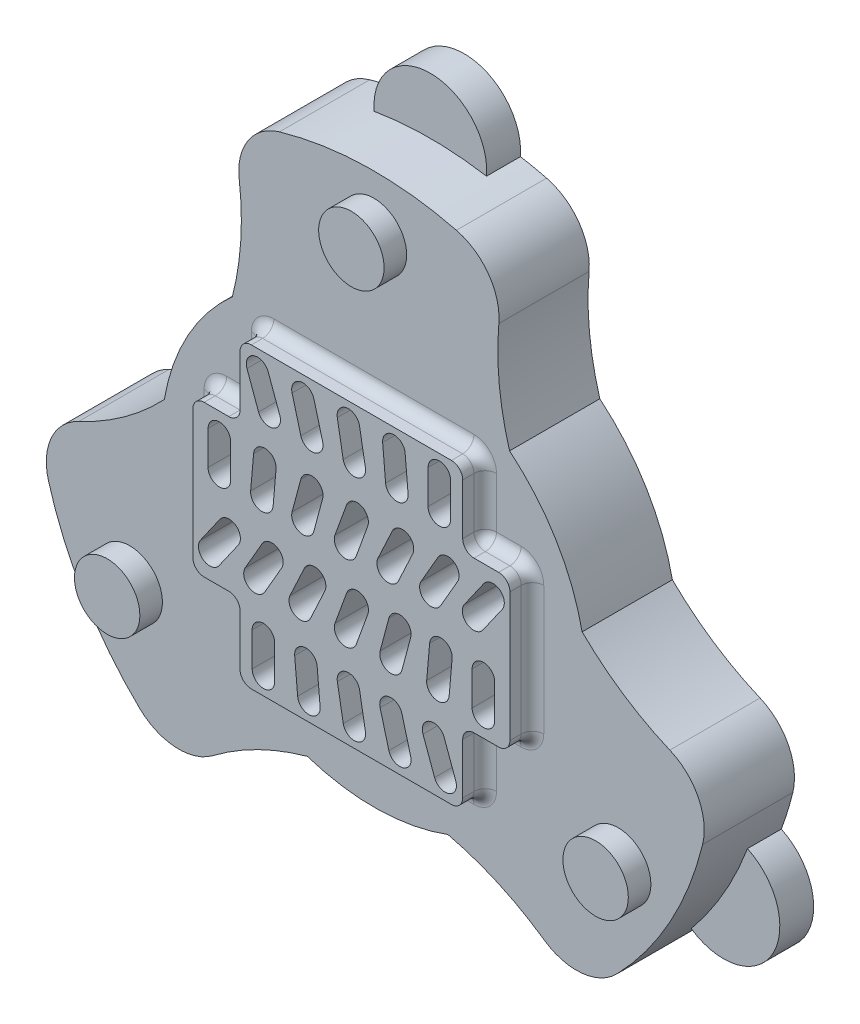
SolidWorks part; units mm, degrees
ref_plane "Спереди" through (0, 0, 0) normal (0, 0, 1) x (1, 0, 0)
ref_plane "Сверху" through (0, 0, 0) normal (0, 1, 0) x (1, 0, 0)
ref_plane "Справа" through (0, 0, 0) normal (1, 0, 0) x (0, 0, -1)
sketch "Sketch1" plane through (0, 0, 0) normal (0, 0, 1) x (1, 0, 0)
  line L0 (3.9, 6.755) -> (7.8, 0) construction
  line L2 (5.85, 10.1325) -> (11.7, 0) construction
  line L4 (7.8, 13.51) -> (15.6, 0) construction
  circle A61 centre (0, 0) radius 20
  circle A131 centre (0, 0) radius 1.25
  circle A484 centre (3.9, 0) radius 1.25
  circle A485 centre (7.8, 0) radius 1.25
  circle A486 centre (11.7, 0) radius 1.25
  circle A487 centre (15.6, 0) radius 1.25
  circle A488 centre (1.95, -3.3775) radius 1.25
  circle A489 centre (3.9, -6.755) radius 1.25
  circle A490 centre (5.85, -10.1325) radius 1.25
  circle A491 centre (7.8, -13.51) radius 1.25
  circle A492 centre (-1.95, -3.3775) radius 1.25
  circle A493 centre (-3.9, -6.755) radius 1.25
  circle A494 centre (-5.85, -10.1325) radius 1.25
  circle A495 centre (-7.8, -13.51) radius 1.25
  circle A496 centre (-3.9, 0) radius 1.25
  circle A497 centre (-7.8, 0) radius 1.25
  circle A498 centre (-11.7, 0) radius 1.25
  circle A499 centre (-15.6, 0) radius 1.25
  circle A500 centre (-1.95, 3.3775) radius 1.25
  circle A501 centre (-3.9, 6.755) radius 1.25
  circle A502 centre (-5.85, 10.1325) radius 1.25
  circle A503 centre (-7.8, 13.51) radius 1.25
  circle A504 centre (1.95, 3.3775) radius 1.25
  circle A505 centre (3.9, 6.755) radius 1.25
  circle A506 centre (5.85, 10.1325) radius 1.25
  circle A507 centre (7.8, 13.51) radius 1.25
  circle A508 centre (5.85, 3.3775) radius 1.25
  circle A509 centre (7.8, 6.755) radius 1.25
  circle A510 centre (9.75, 3.3775) radius 1.25
  circle A511 centre (11.7, 6.755) radius 1.25
  circle A512 centre (9.7491, 10.1341) radius 1.25
  circle A513 centre (13.6509, 3.3759) radius 1.25
  circle A514 centre (5.85, -3.3791) radius 1.25
  circle A515 centre (9.75, -3.3791) radius 1.25
  circle A516 centre (7.8, -6.7566) radius 1.25
  circle A517 centre (11.7, -6.7566) radius 1.25
  circle A518 centre (9.7491, -10.1356) radius 1.25
  circle A519 centre (13.6509, -3.3775) radius 1.25
  circle A520 centre (-0.0013, -6.7573) radius 1.25
  circle A521 centre (1.9487, -10.1348) radius 1.25
  circle A522 centre (-1.9513, -10.1348) radius 1.25
  circle A523 centre (-0.0013, -13.5123) radius 1.25
  circle A524 centre (-3.9032, -13.5123) radius 1.25
  circle A525 centre (3.9005, -13.5123) radius 1.25
  circle A526 centre (-5.8527, -3.3791) radius 1.25
  circle A527 centre (-7.8027, -6.7566) radius 1.25
  circle A528 centre (-9.7527, -3.3791) radius 1.25
  circle A529 centre (-11.7027, -6.7566) radius 1.25
  circle A530 centre (-13.6536, -3.3775) radius 1.25
  circle A531 centre (-9.7518, -10.1356) radius 1.25
  circle A532 centre (-5.8527, 3.3775) radius 1.25
  circle A533 centre (-9.7527, 3.3775) radius 1.25
  circle A534 centre (-7.8027, 6.755) radius 1.25
  circle A535 centre (-11.7027, 6.755) radius 1.25
  circle A536 centre (-9.7518, 10.1341) radius 1.25
  circle A537 centre (-13.6536, 3.3759) radius 1.25
  circle A538 centre (-0.0014, 6.7558) radius 1.25
  circle A539 centre (-1.9514, 10.1333) radius 1.25
  circle A540 centre (1.9486, 10.1333) radius 1.25
  circle A541 centre (-0.0014, 13.5108) radius 1.25
  circle A542 centre (3.9005, 13.5108) radius 1.25
  circle A543 centre (-3.9032, 13.5108) radius 1.25
  circle A544 centre (13.65, -1.1258) radius 2.2517 construction
  circle A545 centre (11.7009, -4.5044) radius 2.2522 construction
  circle A546 centre (9.75, -7.8834) radius 2.2522 construction
  circle A547 centre (7.7987, -11.2591) radius 2.2509 construction
  circle A548 centre (13.65, -1.1258) radius 0.65
  circle A549 centre (11.7009, -4.5044) radius 0.65
  circle A550 centre (9.75, -7.8834) radius 0.65
  circle A551 centre (7.7987, -11.2591) radius 0.65
  circle A552 centre (9.75, -1.1258) radius 0.65
  circle A553 centre (7.8009, -4.5044) radius 0.65
  circle A554 centre (5.85, -7.8834) radius 0.65
  circle A555 centre (3.8987, -11.2591) radius 0.65
  circle A556 centre (5.85, -1.1258) radius 0.65
  circle A557 centre (3.9009, -4.5044) radius 0.65
  circle A558 centre (1.95, -7.8834) radius 0.65
  circle A559 centre (-0.0013, -11.2591) radius 0.65
  circle A560 centre (1.95, -1.1258) radius 0.65
  circle A561 centre (0.0009, -4.5044) radius 0.65
  circle A562 centre (-1.95, -7.8834) radius 0.65
  circle A563 centre (-3.9013, -11.2591) radius 0.65
  circle A564 centre (-1.95, -1.1258) radius 0.65
  circle A565 centre (-3.8991, -4.5044) radius 0.65
  circle A566 centre (-5.85, -7.8834) radius 0.65
  circle A567 centre (-7.8013, -11.2591) radius 0.65
  circle A568 centre (-5.85, -1.1258) radius 0.65
  circle A569 centre (-7.7991, -4.5044) radius 0.65
  circle A570 centre (-9.75, -7.8834) radius 0.65
  circle A572 centre (-9.75, -1.1258) radius 0.65
  circle A573 centre (-11.6991, -4.5044) radius 0.65
  circle A576 centre (-13.65, -1.1258) radius 0.65
  circle A587 centre (0, 2.2517) radius 2.2517 construction
  circle A588 centre (0, 2.2517) radius 0.65
  circle A589 centre (3.9, 2.2517) radius 0.65
  circle A590 centre (7.8, 2.2517) radius 0.65
  circle A591 centre (11.7, 2.2517) radius 0.65
  circle A592 centre (15.6, 2.2517) radius 0.65
  circle A593 centre (1.9491, 5.6297) radius 2.2522 construction
  circle A594 centre (1.9491, 5.6297) radius 0.65
  circle A595 centre (5.8491, 5.6297) radius 0.65
  circle A596 centre (9.7491, 5.6297) radius 0.65
  circle A597 centre (13.6491, 5.6297) radius 0.65
  circle A598 centre (3.8991, 9.0072) radius 2.2522 construction
  circle A599 centre (3.8991, 9.0072) radius 0.65
  circle A600 centre (7.7991, 9.0072) radius 0.65
  circle A601 centre (11.6991, 9.0072) radius 0.65
  circle A602 centre (5.85, 12.3842) radius 2.2517 construction
  circle A603 centre (5.85, 12.3842) radius 0.65
  circle A604 centre (9.75, 12.3842) radius 0.65
  circle A605 centre (5.85, -14.6358) radius 0.65
  circle A606 centre (1.9509, -14.6353) radius 0.65
  circle A607 centre (-1.9491, -14.6353) radius 0.65
  circle A608 centre (-5.85, -14.6358) radius 0.65
  circle A609 centre (-15.6, 2.2517) radius 0.65
  circle A610 centre (-13.65, 5.6281) radius 0.65
  circle A611 centre (-11.7, 9.0056) radius 0.65
  circle A612 centre (-9.75, 12.3842) radius 0.65
  circle A613 centre (-5.85, 12.3842) radius 0.65
  circle A614 centre (-1.95, 12.3842) radius 0.65
  circle A615 centre (1.95, 12.3842) radius 0.65
  circle A616 centre (-7.8, 9.0056) radius 0.65
  circle A617 centre (-9.75, 5.6281) radius 0.65
  circle A618 centre (-11.7, 2.2517) radius 0.65
  circle A619 centre (-3.9, 9.0056) radius 0.65
  circle A620 centre (-5.85, 5.6281) radius 0.65
  circle A621 centre (-7.8, 2.2517) radius 0.65
  circle A622 centre (0, 9.0056) radius 0.65
  circle A623 centre (-1.95, 5.6281) radius 0.65
  circle A624 centre (-3.9, 2.2517) radius 0.65
  circle A625 centre (-15.5991, -4.5044) radius 0.65
  circle A626 centre (-13.65, -7.8834) radius 0.65
  circle A627 centre (-17.55, -7.8834) radius 0.65
  circle A628 centre (-19.5013, -11.2591) radius 0.65
  circle A629 centre (-15.6013, -11.2591) radius 0.65
  circle A630 centre (-11.7013, -11.2591) radius 0.65
  point P51 (0, 0)
  point P125 (-0.0013, -0.0008)
  point P231 (0, 0)
  dimension "D1" = 5
  dimension "D3" = 6
  dimension "D5" = 8
  dimension "D7" = 4
  dimension "D11" = 4
  dimension "D2" = 6
  dimension "D6" = 5
  dimension "D8" = 3
  dimension "D9" = 2
  dimension "D4" = 1.3
  dimension "D10" = 3
ref_plane "Plane1" through (0, 0, 10) normal (0, 0, 1) x (1, 0, 0)
sketch "Sketch2" plane through (0, 0, 10) normal (0, 0, 1) x (1, 0, 0)
  line L2 (8.0291, 21.9345) -> (-10.7971, 21.9345) construction
  circle A52 centre (0, 0) radius 16.85 construction
  circle A53 centre (0, 0) radius 18.85
  point P5 (0, 0)
  line B0 (4.7641, 11.7139) -> (5.0256, 8.7254)
  arc B1 (3.0332, 8.551) -> (5.0256, 8.7254) centre (4.0294, 8.6382) ccw
  line B2 (2.7717, 11.5396) -> (3.0332, 8.551)
  arc B3 (4.7641, 11.7139) -> (2.7717, 11.5396) centre (3.7679, 11.6268) ccw
  line B4 (3.7679, 11.6268) -> (4.0294, 8.6382) construction
  line B5 (0.722, 11.7838) -> (1.2429, 8.8293)
  arc B6 (-0.7267, 8.482) -> (1.2429, 8.8293) centre (0.2581, 8.6557) ccw
  line B7 (-1.2476, 11.4365) -> (-0.7267, 8.482)
  arc B8 (0.722, 11.7838) -> (-1.2476, 11.4365) centre (-0.2628, 11.6101) ccw
  line B9 (-0.2628, 11.6101) -> (0.2581, 8.6557) construction
  line B10 (-3.3247, 11.8406) -> (-2.5482, 8.9428)
  arc B11 (-4.48, 8.4252) -> (-2.5482, 8.9428) centre (-3.5141, 8.684) ccw
  line B12 (-5.2565, 11.323) -> (-4.48, 8.4252)
  arc B13 (-3.3247, 11.8406) -> (-5.2565, 11.323) centre (-4.2906, 11.5818) ccw
  line B14 (-4.2906, 11.5818) -> (-3.5141, 8.684) construction
  line B15 (-7.3747, 11.8841) -> (-6.3486, 9.065)
  arc B16 (-8.228, 8.3809) -> (-6.3486, 9.065) centre (-7.2883, 8.723) ccw
  line B17 (-9.2541, 11.2) -> (-8.228, 8.3809)
  arc B18 (-7.3747, 11.8841) -> (-9.2541, 11.2) centre (-8.3144, 11.542) ccw
  line B19 (-8.3144, 11.542) -> (-7.2883, 8.723) construction
  line B20 (10.0165, 2.7228) -> (11.7373, 5.1803)
  arc B21 (13.3756, 4.0332) -> (11.7373, 5.1803) centre (12.5564, 4.6067) ccw
  line B22 (11.6548, 1.5757) -> (13.3756, 4.0332)
  arc B23 (10.0165, 2.7228) -> (11.6548, 1.5757) centre (10.8357, 2.1493) ccw
  line B24 (10.8357, 2.1493) -> (12.5564, 4.6067) construction
  line B25 (6.18, 2.579) -> (7.68, 5.177)
  arc B26 (9.4121, 4.177) -> (7.68, 5.177) centre (8.546, 4.677) ccw
  line B27 (7.9121, 1.579) -> (9.4121, 4.177)
  arc B28 (6.18, 2.579) -> (7.9121, 1.579) centre (7.046, 2.079) ccw
  line B29 (7.046, 2.079) -> (8.546, 4.677) construction
  line B30 (2.3558, 2.4412) -> (3.6237, 5.1601)
  arc B31 (5.4363, 4.3148) -> (3.6237, 5.1601) centre (4.53, 4.7375) ccw
  line B32 (4.1684, 1.5959) -> (5.4363, 4.3148)
  arc B33 (2.3558, 2.4412) -> (4.1684, 1.5959) centre (3.2621, 2.0185) ccw
  line B34 (3.2621, 2.0185) -> (4.53, 4.7375) construction
  line B35 (-1.4567, 2.3105) -> (-0.4306, 5.1296)
  arc B36 (1.4488, 4.4455) -> (-0.4306, 5.1296) centre (0.5091, 4.7875) ccw
  line B37 (0.4227, 1.6264) -> (1.4488, 4.4455)
  arc B38 (-1.4567, 2.3105) -> (0.4227, 1.6264) centre (-0.517, 1.9685) ccw
  line B39 (-0.517, 1.9685) -> (0.5091, 4.7875) construction
  line B40 (-5.2581, 2.1879) -> (-4.4816, 5.0857)
  arc B41 (-2.5498, 4.5681) -> (-4.4816, 5.0857) centre (-3.5157, 4.8269) ccw
  line B42 (-3.3263, 1.6703) -> (-2.5498, 4.5681)
  arc B43 (-5.2581, 2.1879) -> (-3.3263, 1.6703) centre (-4.2922, 1.9291) ccw
  line B44 (-4.2922, 1.9291) -> (-3.5157, 4.8269) construction
  line B45 (-8.9296, 1.9704) -> (-8.6682, 4.9589)
  arc B46 (-6.6758, 4.7846) -> (-8.6682, 4.9589) centre (-7.672, 4.8718) ccw
  line B47 (-6.9372, 1.7961) -> (-6.6758, 4.7846)
  arc B48 (-8.9296, 1.9704) -> (-6.9372, 1.7961) centre (-7.9334, 1.8832) ccw
  line B49 (-7.9334, 1.8832) -> (-7.672, 4.8718) construction
  line B50 (-12.704, 1.878) -> (-12.704, 4.878)
  arc B51 (-10.704, 4.878) -> (-12.704, 4.878) centre (-11.704, 4.878) ccw
  line B52 (-10.704, 1.878) -> (-10.704, 4.878)
  arc B53 (-12.704, 1.878) -> (-10.704, 1.878) centre (-11.704, 1.878) ccw
  line B54 (-11.704, 1.878) -> (-11.704, 4.878) construction
  line B55 (8.7976, 11.6329) -> (8.7976, 8.6329)
  arc B56 (6.7976, 8.6329) -> (8.7976, 8.6329) centre (7.7976, 8.6329) ccw
  line B57 (6.7976, 11.6329) -> (6.7976, 8.6329)
  arc B58 (8.7976, 11.6329) -> (6.7976, 11.6329) centre (7.7976, 11.6329) ccw
  line B59 (-4.7641, -11.7139) -> (-5.0256, -8.7254)
  arc B60 (-3.0332, -8.551) -> (-5.0256, -8.7254) centre (-4.0294, -8.6382) ccw
  line B61 (-2.7717, -11.5396) -> (-3.0332, -8.551)
  arc B62 (-4.7641, -11.7139) -> (-2.7717, -11.5396) centre (-3.7679, -11.6268) ccw
  line B63 (-0.722, -11.7838) -> (-1.2429, -8.8293)
  arc B64 (0.7267, -8.482) -> (-1.2429, -8.8293) centre (-0.2581, -8.6557) ccw
  line B65 (1.2476, -11.4365) -> (0.7267, -8.482)
  arc B66 (-0.722, -11.7838) -> (1.2476, -11.4365) centre (0.2628, -11.6101) ccw
  line B67 (3.3247, -11.8406) -> (2.5482, -8.9428)
  arc B68 (4.48, -8.4252) -> (2.5482, -8.9428) centre (3.5141, -8.684) ccw
  line B69 (5.2565, -11.323) -> (4.48, -8.4252)
  arc B70 (3.3247, -11.8406) -> (5.2565, -11.323) centre (4.2906, -11.5818) ccw
  line B71 (7.3747, -11.8841) -> (6.3486, -9.065)
  arc B72 (8.228, -8.3809) -> (6.3486, -9.065) centre (7.2883, -8.723) ccw
  line B73 (9.2541, -11.2) -> (8.228, -8.3809)
  arc B74 (7.3747, -11.8841) -> (9.2541, -11.2) centre (8.3144, -11.542) ccw
  line B75 (-10.0165, -2.7228) -> (-11.7373, -5.1803)
  arc B76 (-13.3756, -4.0332) -> (-11.7373, -5.1803) centre (-12.5564, -4.6067) ccw
  line B77 (-11.6548, -1.5757) -> (-13.3756, -4.0332)
  arc B78 (-10.0165, -2.7228) -> (-11.6548, -1.5757) centre (-10.8357, -2.1493) ccw
  line B79 (-6.18, -2.579) -> (-7.68, -5.177)
  arc B80 (-9.4121, -4.177) -> (-7.68, -5.177) centre (-8.546, -4.677) ccw
  line B81 (-7.9121, -1.579) -> (-9.4121, -4.177)
  arc B82 (-6.18, -2.579) -> (-7.9121, -1.579) centre (-7.046, -2.079) ccw
  line B83 (-2.3558, -2.4412) -> (-3.6237, -5.1601)
  arc B84 (-5.4363, -4.3148) -> (-3.6237, -5.1601) centre (-4.53, -4.7375) ccw
  line B85 (-4.1684, -1.5959) -> (-5.4363, -4.3148)
  arc B86 (-2.3558, -2.4412) -> (-4.1684, -1.5959) centre (-3.2621, -2.0185) ccw
  line B87 (1.4567, -2.3105) -> (0.4306, -5.1296)
  arc B88 (-1.4488, -4.4455) -> (0.4306, -5.1296) centre (-0.5091, -4.7875) ccw
  line B89 (-0.4227, -1.6264) -> (-1.4488, -4.4455)
  arc B90 (1.4567, -2.3105) -> (-0.4227, -1.6264) centre (0.517, -1.9685) ccw
  line B91 (5.2581, -2.1879) -> (4.4816, -5.0857)
  arc B92 (2.5498, -4.5681) -> (4.4816, -5.0857) centre (3.5157, -4.8269) ccw
  line B93 (3.3263, -1.6703) -> (2.5498, -4.5681)
  arc B94 (5.2581, -2.1879) -> (3.3263, -1.6703) centre (4.2922, -1.9291) ccw
  line B95 (8.9296, -1.9704) -> (8.6682, -4.9589)
  arc B96 (6.6758, -4.7846) -> (8.6682, -4.9589) centre (7.672, -4.8718) ccw
  line B97 (6.9372, -1.7961) -> (6.6758, -4.7846)
  arc B98 (8.9296, -1.9704) -> (6.9372, -1.7961) centre (7.9334, -1.8832) ccw
  line B99 (12.704, -1.878) -> (12.704, -4.878)
  arc B100 (10.704, -4.878) -> (12.704, -4.878) centre (11.704, -4.878) ccw
  line B101 (10.704, -1.878) -> (10.704, -4.878)
  arc B102 (12.704, -1.878) -> (10.704, -1.878) centre (11.704, -1.878) ccw
  line B103 (-8.7976, -11.6329) -> (-8.7976, -8.6329)
  arc B104 (-6.7976, -8.6329) -> (-8.7976, -8.6329) centre (-7.7976, -8.6329) ccw
  line B105 (-6.7976, -11.6329) -> (-6.7976, -8.6329)
  arc B106 (-8.7976, -11.6329) -> (-6.7976, -11.6329) centre (-7.7976, -11.6329) ccw
  dimension "D15" = 2
  dimension "D2" = 95
  dimension "D4" = 105
  dimension "D5" = 110
  dimension "D6" = 55
  dimension "D7" = 60
  dimension "D9" = 70
  dimension "D12" = 90
  dimension "D13" = 2
  dimension "D3" = 100
  dimension "D8" = 65
  dimension "D10" = 75
  dimension "D11" = 85
sketch_block_instance "Block4-1"
sketch_block "Block4"
sketch_block_instance "Block5-1"
sketch_block "Block5"
sketch_block_instance "Block6-1"
sketch_block "Block6"
sketch_block_instance "Block7-1"
sketch_block "Block7" parameters "D1"=2, "D2"=3
sketch_block_instance "Block8-1"
sketch_block "Block8"
sketch_block_instance "Block9-1"
sketch_block "Block9"
sketch_block_instance "Block10-1"
sketch_block "Block10"
sketch_block_instance "Block11-1"
sketch_block "Block11"
sketch_block_instance "Block12-1"
sketch_block "Block12"
sketch_block_instance "Block13-1"
sketch_block "Block13" parameters "D1"=2, "D2"=3
sketch_block_instance "Block14-1"
sketch_block "Block14"
sketch_block_instance "Block28-1"
sketch_block "Block28"
sketch_block_instance "Block4-2"
sketch_block_instance "Block5-2"
sketch_block_instance "Block6-2"
sketch_block_instance "Block7-2"
sketch_block_instance "Block8-2"
sketch_block_instance "Block9-2"
sketch_block_instance "Block10-2"
sketch_block_instance "Block11-2"
sketch_block_instance "Block12-2"
sketch_block_instance "Block13-2"
sketch_block_instance "Block14-2"
sketch_block_instance "Block28-2"
extrude "Boss-Extrude1" add sketch "Sketch2" along normal blind 8
sketch "Sketch3" plane through (0, 0, 18) normal (0, 0, 1) x (1, 0, 0)
  circle A0 centre (0, 0) radius 17.6
  circle A1 centre (0, 0) radius 30
extrude "Boss-Extrude2" add sketch "Sketch3" against normal up to surface (8 mm away) up to face at (11.704, -3.378, 10)
sketch "Sketch4" plane through (0, 0, 18) normal (0, 0, 1) x (1, 0, 0)
  circle A0 centre (0, 0) radius 25 construction
  circle A1 centre (0, 25) radius 2.9
  circle A2 centre (21.6506, -12.5) radius 2.9
  circle A3 centre (-21.6506, -12.5) radius 2.9
  point P11 (0, 0)
  dimension "D1" = 3
extrude "Boss-Extrude3" add sketch "Sketch4" along normal blind 2
sketch "Sketch6" plane through (0, 0, 10) normal (0, 0, -1) x (-1, 0, 0)
  circle A0 centre (0, 30) radius 5
  circle A1 centre (0, 0) radius 30 construction
  circle A2 centre (25.9808, -15) radius 5
  circle A3 centre (-25.9808, -15) radius 5
  point P10 (0, 0)
  dimension "D1" = 3
extrude "Boss-Extrude4" add sketch "Sketch6" against normal blind 3
sketch "Sketch5" plane through (0, 0, 10) normal (0, 0, -1) x (-1, 0, 0)
  circle A0 centre (0, 25) radius 3
  circle A1 centre (21.6506, -12.5) radius 3
  circle A2 centre (-21.6506, -12.5) radius 3
extrude "Cut-Extrude1" cut sketch "Sketch5" against normal blind 3
sketch "Sketch7" plane through (0, 0, 10) normal (0, 0, -1) x (-1, 0, 0)
  line L0 (0, 0) -> (-35.9801, 21.6664) construction
  circle A0 centre (0, 0) radius 42 construction
  circle A1 centre (-35.9801, 21.6664) radius 25
  circle A2 centre (36.7537, 20.3265) radius 25
  circle A3 centre (-0.7736, -41.9929) radius 25
  point P11 (0, 0)
  dimension "D1" = 3
extrude "Cut-Extrude2" cut sketch "Sketch7" against normal blind 8
fillet "Fillet1" radius 5 6 edges at (-12.7099, 27.1746, 14) (-29.7735, -3.6793, 14) (-17.1789, -24.5944, 14) (18.0731, -23.945, 14) (29.8888, -2.5802, 14) (11.7004, 27.6243, 14)
sketch "Sketch8"
sketch_block_instance "Block1-1"
sketch_block "Block1" parameters "D1"=2, "D2"=3
sketch_block_instance "Block3-1"
sketch_block "Block3" parameters "D1"=2, "D2"=3
sketch "Sketch9" plane through (0, 0, 0) normal (0, 0, 1) x (1, 0, 0)
  line L0 (-7.8, 13.51) -> (-7.8027, 6.755) construction
  line L1 (-9.7518, 10.1341) -> (-5.85, 10.1325) construction
  line L2 (-7.8008, 11.6325) -> (-7.8019, 8.6325) construction
  line L3 (-6.8008, 11.6321) -> (-6.8019, 8.6321)
  line L4 (-8.8008, 11.6329) -> (-8.8019, 8.6329)
  line L5 (-4.9008, 11.6329) -> (-4.9019, 8.6329)
  line L6 (-2.9008, 11.6321) -> (-2.9019, 8.6321)
  line L7 (-3.9008, 11.6325) -> (-3.9019, 8.6325) construction
  line L8 (-1.0008, 11.6329) -> (-1.0019, 8.6329)
  line L9 (0.9992, 11.6321) -> (0.9981, 8.6321)
  line L10 (-0.0008, 11.6325) -> (-0.0019, 8.6325) construction
  line L11 (2.8992, 11.6329) -> (2.8981, 8.6329)
  line L12 (4.8992, 11.6321) -> (4.8981, 8.6321)
  line L13 (3.8992, 11.6325) -> (3.8981, 8.6325) construction
  line L14 (6.7992, 11.6329) -> (6.7981, 8.6329)
  line L15 (8.7992, 11.6321) -> (8.7981, 8.6321)
  line L16 (7.7992, 11.6325) -> (7.7981, 8.6325) construction
  line L17 (-9.7518, 10.1341) -> (-9.7527, 3.3775) construction
  line L18 (-11.7027, 6.755) -> (-7.8027, 6.755) construction
  line L19 (-10.7035, 1.877) -> (-10.702, 4.877)
  line L22 (-9.7527, 3.3775) -> (-5.8527, 3.3775) construction
  line L25 (-7.8027, 6.755) -> (-7.8, 0) construction
  line L26 (-7.8035, 1.8775) -> (-7.8019, 4.8775) construction
  line L27 (-8.8035, 1.878) -> (-8.8019, 4.878)
  line L28 (-6.8035, 1.877) -> (-6.8019, 4.877)
  line L29 (-2.9035, 1.877) -> (-2.9019, 4.877)
  line L30 (-4.9035, 1.878) -> (-4.9019, 4.878)
  line L31 (-3.9035, 1.8775) -> (-3.9019, 4.8775) construction
  line L32 (0.9965, 1.877) -> (0.9981, 4.877)
  line L33 (-1.0035, 1.878) -> (-1.0019, 4.878)
  line L34 (-0.0035, 1.8775) -> (-0.0019, 4.8775) construction
  line L35 (4.8965, 1.877) -> (4.8981, 4.877)
  line L36 (2.8965, 1.878) -> (2.8981, 4.878)
  line L37 (3.8965, 1.8775) -> (3.8981, 4.8775) construction
  line L38 (8.7965, 1.877) -> (8.7981, 4.877)
  line L39 (6.7965, 1.878) -> (6.7981, 4.878)
  line L40 (7.7965, 1.8775) -> (7.7981, 4.8775) construction
  line L41 (12.6965, 1.877) -> (12.6981, 4.877)
  line L42 (10.6965, 1.878) -> (10.6981, 4.878)
  line L43 (11.6965, 1.8775) -> (11.6981, 4.8775) construction
  line L44 (-12.7035, 1.878) -> (-12.7019, 4.878)
  line L45 (-11.7035, 1.8775) -> (-11.702, 4.8775) construction
  line L46 (-9.7527, -3.3791) -> (-5.8527, -3.3791) construction
  line L47 (-7.8, 0) -> (-7.8027, -6.7566) construction
  line L48 (-7.8046, -4.8791) -> (-7.8008, -1.8791) construction
  line L49 (-8.8046, -4.8778) -> (-8.8008, -1.8778)
  line L50 (-6.8046, -4.8804) -> (-6.8008, -1.8804)
  line L51 (-2.9046, -4.8804) -> (-2.9008, -1.8804)
  line L52 (-4.9046, -4.8778) -> (-4.9008, -1.8778)
  line L53 (-3.9046, -4.8791) -> (-3.9008, -1.8791) construction
  line L54 (0.9954, -4.8804) -> (0.9992, -1.8804)
  line L55 (-1.0046, -4.8778) -> (-1.0008, -1.8778)
  line L56 (-0.0046, -4.8791) -> (-0.0008, -1.8791) construction
  line L57 (4.8954, -4.8804) -> (4.8992, -1.8804)
  line L58 (2.8954, -4.8778) -> (2.8992, -1.8778)
  line L59 (3.8954, -4.8791) -> (3.8992, -1.8791) construction
  line L60 (8.7954, -4.8804) -> (8.7992, -1.8804)
  line L61 (6.7954, -4.8778) -> (6.7992, -1.8778)
  line L62 (7.7954, -4.8791) -> (7.7992, -1.8791) construction
  line L63 (12.6954, -4.8804) -> (12.6992, -1.8804)
  line L64 (10.6954, -4.8778) -> (10.6992, -1.8778)
  line L65 (11.6954, -4.8791) -> (11.6992, -1.8791) construction
  line L66 (-10.7046, -4.8804) -> (-10.7008, -1.8804)
  line L67 (-12.7046, -4.8778) -> (-12.7008, -1.8778)
  line L68 (-11.7046, -4.8791) -> (-11.7008, -1.8791) construction
  line L69 (-9.7518, -10.1356) -> (-5.482, -10.1356) construction
  line L70 (-7.8027, -6.7566) -> (-7.8, -13.51) construction
  line L71 (-7.8007, -8.6356) -> (-7.8007, -11.6356) construction
  line L72 (-6.8007, -8.6356) -> (-6.8007, -11.6356)
  line L73 (-8.8007, -8.6356) -> (-8.8007, -11.6356)
  line L74 (-4.9007, -8.6356) -> (-4.9007, -11.6356)
  line L75 (-2.9007, -8.6356) -> (-2.9007, -11.6356)
  line L76 (-3.9007, -8.6356) -> (-3.9007, -11.6356) construction
  line L77 (-1.0007, -8.6356) -> (-1.0007, -11.6356)
  line L78 (0.9993, -8.6356) -> (0.9993, -11.6356)
  line L79 (-0.0007, -8.6356) -> (-0.0007, -11.6356) construction
  line L80 (2.8993, -8.6356) -> (2.8993, -11.6356)
  line L81 (4.8993, -8.6356) -> (4.8993, -11.6356)
  line L82 (3.8993, -8.6356) -> (3.8993, -11.6356) construction
  line L83 (6.7993, -8.6356) -> (6.7993, -11.6356)
  line L84 (8.7993, -8.6356) -> (8.7993, -11.6356)
  line L85 (7.7993, -8.6356) -> (7.7993, -11.6356) construction
  arc A0 (-6.8008, 11.6321) -> (-8.8008, 11.6329) centre (-7.8008, 11.6325) ccw
  arc A1 (-8.8019, 8.6329) -> (-6.8019, 8.6321) centre (-7.8019, 8.6325) ccw
  arc A2 (-2.9008, 11.6321) -> (-4.9008, 11.6329) centre (-3.9008, 11.6325) ccw
  arc A3 (-4.9019, 8.6329) -> (-2.9019, 8.6321) centre (-3.9019, 8.6325) ccw
  arc A4 (0.9992, 11.6321) -> (-1.0008, 11.6329) centre (-0.0008, 11.6325) ccw
  arc A5 (-1.0019, 8.6329) -> (0.9981, 8.6321) centre (-0.0019, 8.6325) ccw
  arc A6 (4.8992, 11.6321) -> (2.8992, 11.6329) centre (3.8992, 11.6325) ccw
  arc A7 (2.8981, 8.6329) -> (4.8981, 8.6321) centre (3.8981, 8.6325) ccw
  arc A8 (8.7992, 11.6321) -> (6.7992, 11.6329) centre (7.7992, 11.6325) ccw
  arc A9 (6.7981, 8.6329) -> (8.7981, 8.6321) centre (7.7981, 8.6325) ccw
  arc A14 (-8.8035, 1.878) -> (-6.8035, 1.877) centre (-7.8035, 1.8775) ccw
  arc A15 (-6.8019, 4.877) -> (-8.8019, 4.878) centre (-7.8019, 4.8775) ccw
  arc A16 (-4.9035, 1.878) -> (-2.9035, 1.877) centre (-3.9035, 1.8775) ccw
  arc A17 (-2.9019, 4.877) -> (-4.9019, 4.878) centre (-3.9019, 4.8775) ccw
  arc A18 (-1.0035, 1.878) -> (0.9965, 1.877) centre (-0.0035, 1.8775) ccw
  arc A19 (0.9981, 4.877) -> (-1.0019, 4.878) centre (-0.0019, 4.8775) ccw
  arc A20 (2.8965, 1.878) -> (4.8965, 1.877) centre (3.8965, 1.8775) ccw
  arc A21 (4.8981, 4.877) -> (2.8981, 4.878) centre (3.8981, 4.8775) ccw
  arc A22 (6.7965, 1.878) -> (8.7965, 1.877) centre (7.7965, 1.8775) ccw
  arc A23 (8.7981, 4.877) -> (6.7981, 4.878) centre (7.7981, 4.8775) ccw
  arc A24 (10.6965, 1.878) -> (12.6965, 1.877) centre (11.6965, 1.8775) ccw
  arc A25 (12.6981, 4.877) -> (10.6981, 4.878) centre (11.6981, 4.8775) ccw
  arc A26 (-12.7035, 1.878) -> (-10.7035, 1.877) centre (-11.7035, 1.8775) ccw
  arc A27 (-10.702, 4.877) -> (-12.7019, 4.878) centre (-11.702, 4.8775) ccw
  arc A28 (-8.8046, -4.8778) -> (-6.8046, -4.8804) centre (-7.8046, -4.8791) ccw
  arc A29 (-6.8008, -1.8804) -> (-8.8008, -1.8778) centre (-7.8008, -1.8791) ccw
  arc A30 (-4.9046, -4.8778) -> (-2.9046, -4.8804) centre (-3.9046, -4.8791) ccw
  arc A31 (-2.9008, -1.8804) -> (-4.9008, -1.8778) centre (-3.9008, -1.8791) ccw
  arc A32 (-1.0046, -4.8778) -> (0.9954, -4.8804) centre (-0.0046, -4.8791) ccw
  arc A33 (0.9992, -1.8804) -> (-1.0008, -1.8778) centre (-0.0008, -1.8791) ccw
  arc A34 (2.8954, -4.8778) -> (4.8954, -4.8804) centre (3.8954, -4.8791) ccw
  arc A35 (4.8992, -1.8804) -> (2.8992, -1.8778) centre (3.8992, -1.8791) ccw
  arc A36 (6.7954, -4.8778) -> (8.7954, -4.8804) centre (7.7954, -4.8791) ccw
  arc A37 (8.7992, -1.8804) -> (6.7992, -1.8778) centre (7.7992, -1.8791) ccw
  arc A38 (10.6954, -4.8778) -> (12.6954, -4.8804) centre (11.6954, -4.8791) ccw
  arc A39 (12.6992, -1.8804) -> (10.6992, -1.8778) centre (11.6992, -1.8791) ccw
  arc A40 (-12.7046, -4.8778) -> (-10.7046, -4.8804) centre (-11.7046, -4.8791) ccw
  arc A41 (-10.7008, -1.8804) -> (-12.7008, -1.8778) centre (-11.7008, -1.8791) ccw
  arc A42 (-6.8007, -8.6356) -> (-8.8007, -8.6356) centre (-7.8007, -8.6356) ccw
  arc A43 (-8.8007, -11.6356) -> (-6.8007, -11.6356) centre (-7.8007, -11.6356) ccw
  arc A44 (-2.9007, -8.6356) -> (-4.9007, -8.6356) centre (-3.9007, -8.6356) ccw
  arc A45 (-4.9007, -11.6356) -> (-2.9007, -11.6356) centre (-3.9007, -11.6356) ccw
  arc A46 (0.9993, -8.6356) -> (-1.0007, -8.6356) centre (-0.0007, -8.6356) ccw
  arc A47 (-1.0007, -11.6356) -> (0.9993, -11.6356) centre (-0.0007, -11.6356) ccw
  arc A48 (4.8993, -8.6356) -> (2.8993, -8.6356) centre (3.8993, -8.6356) ccw
  arc A49 (2.8993, -11.6356) -> (4.8993, -11.6356) centre (3.8993, -11.6356) ccw
  arc A50 (8.7993, -8.6356) -> (6.7993, -8.6356) centre (7.7993, -8.6356) ccw
  arc A51 (6.7993, -11.6356) -> (8.7993, -11.6356) centre (7.7993, -11.6356) ccw
  circle A52 centre (0, 0) radius 16.85 construction
  circle A53 centre (0, 0) radius 18.85
  point P10 (-7.8014, 10.1325)
  point P18 (-3.9014, 10.1325)
  point P25 (-0.0014, 10.1325)
  point P32 (3.8986, 10.1325)
  point P39 (7.7986, 10.1325)
  point P50 (-11.7027, 3.3775)
  point P58 (-7.8027, 3.3775)
  point P68 (-3.9027, 3.3775)
  point P75 (-0.0027, 3.3775)
  point P82 (3.8973, 3.3775)
  point P89 (7.7973, 3.3775)
  point P96 (11.6973, 3.3775)
  point P108 (-7.8027, -3.3791)
  point P116 (-3.9027, -3.3791)
  point P123 (-0.0027, -3.3791)
  point P130 (3.8973, -3.3791)
  point P137 (7.7973, -3.3791)
  point P144 (11.6973, -3.3791)
  point P151 (-11.7027, -3.3791)
  point P162 (-7.8007, -10.1356)
  point P170 (-3.9007, -10.1356)
  point P177 (-0.0007, -10.1356)
  point P184 (3.8993, -10.1356)
  point P191 (7.7993, -10.1356)
  dimension "D1" = 2
  dimension "D15" = 2
  dimension "D2" = 3
  dimension "D4" = 2
  dimension "D5" = 3
  dimension "D6" = 2
  dimension "D7" = 3
  dimension "D9" = 2
  dimension "D12" = 3
  dimension "D13" = 2
  dimension "D3" = 5
  dimension "D8" = 6
  dimension "D10" = 6
  dimension "D11" = 2
  dimension "D14" = 5
extrude "Boss-Extrude5" add sketch "Sketch2<2>" along normal blind 10
sketch "Sketch2<2>" plane through (0, 0, 10) normal (0, 0, 1) x (1, 0, 0) same geometry as "Sketch2"
sketch "Sketch10" plane through (0, 0, 20) normal (0, 0, 1) x (1, 0, 0)
  line L1 (-9.8683, 13.2069) -> (9.8683, 13.2069)
  line L2 (-9.8683, 13.2069) -> (-9.8683, -13.2069)
  line L3 (-9.8683, -13.2069) -> (9.8683, -13.2069)
  line L4 (9.8683, 13.2069) -> (9.8683, -13.2069)
  line L5 (-9.8683, 13.2069) -> (9.8683, -13.2069) construction
  line L6 (-9.8683, -13.2069) -> (9.8683, 13.2069) construction
  line L7 (-14.0535, 6.7065) -> (14.0535, 6.7065)
  line L8 (-14.0535, 6.7065) -> (-14.0535, -6.7065)
  line L9 (-14.0535, -6.7065) -> (14.0535, -6.7065)
  line L10 (14.0535, 6.7065) -> (14.0535, -6.7065)
  line L11 (-14.0535, 6.7065) -> (14.0535, -6.7065) construction
  line L12 (-14.0535, -6.7065) -> (14.0535, 6.7065) construction
  circle A0 centre (0, 0) radius 21.6778
  point P0 (0, 0)
  point P6 (0, 0)
extrude "Cut-Extrude3" cut sketch "Sketch10" against normal blind 2 contours A0 L7 L10 L9 L4 L3 L2 L8 L1 region at (-21.0647, 0, 20)
fillet "Fillet2" radius 1 23 edges at (-11.9609, -6.7065, 18) (0, -13.2069, 18) (-14.0535, 0, 18) (-9.8683, 9.9567, 18) (11.9609, -6.7065, 18) (9.8683, -6.7065, 19) (9.8683, -13.2069, 19) (9.8683, -9.9567, 18) (-9.8683, -9.9567, 18) (-9.8683, -13.2069, 19) (-9.8683, -6.7065, 19) (-14.0535, -6.7065, 19) (-11.9609, 6.7065, 18) (-14.0535, 6.7065, 19) (-9.8683, 6.7065, 19) (-9.8683, 13.2069, 19) (9.8683, 13.2069, 19) (14.0535, 6.7065, 19) (14.0535, -6.7065, 19) (14.0535, 0, 18) (11.9609, 6.7065, 18) (9.8683, 9.9567, 18) (0, 13.2069, 18)
fillet "Fillet3" radius 1 2 edges at (10.1612, 6.9994, 18.2929) (9.8683, 6.7065, 19.5)
